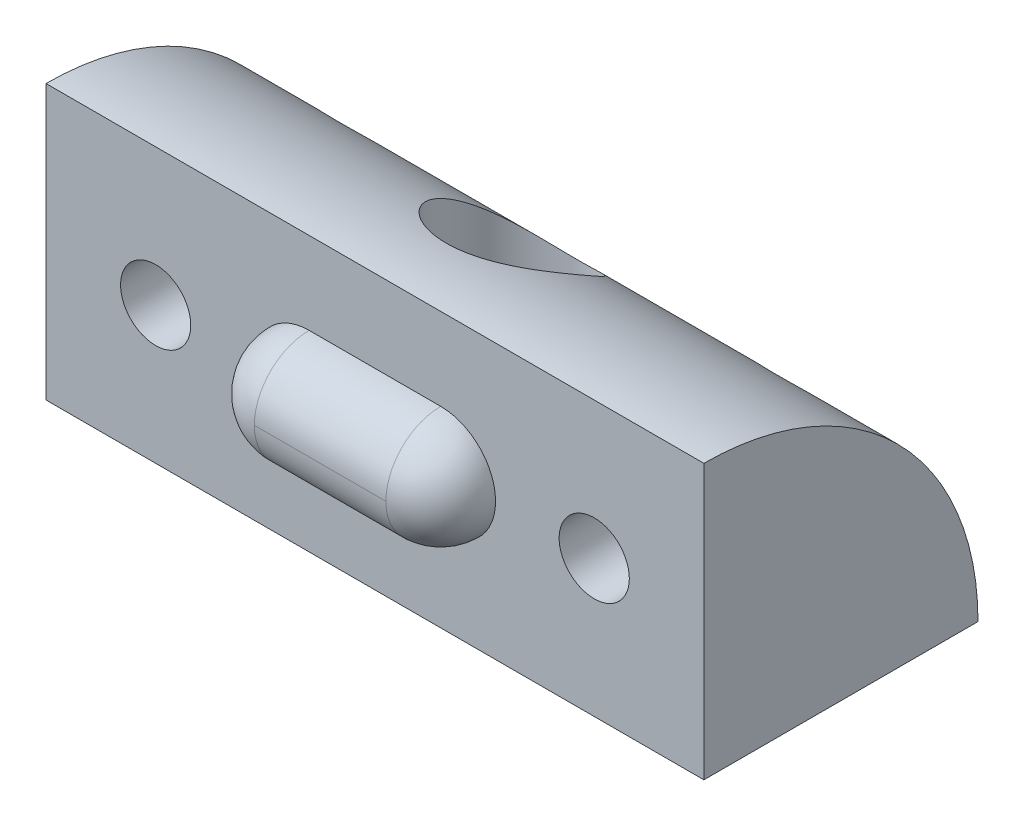
SolidWorks part; units mm, degrees
ref_plane "Alzado" through (0, 0, 0) normal (0, 0, 1) x (1, 0, 0)
ref_plane "Planta" through (0, 0, 0) normal (0, 1, 0) x (1, 0, 0)
ref_plane "Vista lateral" through (0, 0, 0) normal (1, 0, 0) x (0, 0, -1)
sketch "Croquis1" plane through (0, 0, 0) normal (1, 0, 0) x (0, 0, -1)
  line L0 (0, 0) -> (0, 12.5)
  line L1 (0, 0) -> (12.5, 0)
  arc A0 (12.5, 0) -> (0, 12.5) centre (0, 0) ccw
  dimension "D1" = 25
extrude "Saliente-Extruir1" add sketch "Croquis1" along normal blind 70
sketch "Croquis2" plane through (0, 0, 0) normal (0, 0, 1) x (1, 0, 0)
  line L0 (0, 6.25) -> (5, 6.25) construction
  line L1 (0, 12.5) -> (0, 0) construction
  circle A0 centre (5, 6.25) radius 1.6
  circle A1 centre (25, 6.25) radius 1.6
  circle A2 centre (45, 6.25) radius 1.6
  circle A3 centre (65, 6.25) radius 1.6
  dimension "D1" = 4
  dimension "D2" = 3.2
extrude "Cortar-Extruir1" cut sketch "Croquis2" against normal up to next
ref_plane "Plano1" through (0, 0, -4) normal (0, 0, 1) x (1, 0, 0)
sketch "Croquis3" plane through (0, 0, -4) normal (0, 0, 1) x (1, 0, 0)
  circle A0 centre (5, 6.25) radius 3
  circle A1 centre (25, 6.25) radius 3
  circle A2 centre (45, 6.25) radius 3
  circle A3 centre (65, 6.25) radius 3
  dimension "D1" = 4
extrude "Cortar-Extruir2" cut sketch "Croquis3" against normal up to next
sketch "Croquis4" plane through (0, 0, 0) normal (0, -1, 0) x (1, 0, 0)
  line L0 (70, -6.25) -> (55, -6.25) construction
  line L1 (70, 0) -> (70, -12.5) construction
  circle A0 centre (55, -6.25) radius 3
  circle A1 centre (35, -6.25) radius 3
  circle A2 centre (15, -6.25) radius 3
  dimension "D1" = 3
  dimension "D2" = 6
extrude "Cortar-Extruir3" cut sketch "Croquis4" against normal up to next
ref_plane "Plano2" through (0, 10, 0) normal (0, -1, 0) x (-1, 0, 0)
sketch "Croquis6" plane through (0, 0, 0) normal (-1, 0, 0) x (0, 0, 1)
  line L1 (0, 0) -> (-16.8618, 0)
  line L2 (0, 0) -> (0, 17.3809)
  line L3 (0, 17.3809) -> (-16.8618, 17.3809)
  line L4 (-16.8618, 0) -> (-16.8618, 17.3809)
extrude "Cortar-Extruir5" cut sketch "Croquis6" against normal blind 40
sketch "Croquis7" plane through (0, 0, 0) normal (0, 0, 1) x (1, 0, 0)
  line L0 (65, 6.25) -> (45, 6.25) construction
  line L1 (58, 8.75) -> (52, 8.75)
  line L2 (58, 3.75) -> (52, 3.75)
  line L3 (55, 3.75) -> (55, 8.75) construction
  line L4 (55, 12.5) -> (55, 6.25) construction
  line L5 (70, 12.5) -> (40, 12.5) construction
  arc A1 (58, 3.75) -> (58, 8.75) centre (58, 6.25) ccw
  arc A2 (52, 8.75) -> (52, 3.75) centre (52, 6.25) ccw
  point P14 (55, 6.25)
  dimension "D1" = 6
  dimension "D2" = 5
extrude "Saliente-Extruir2" add sketch "Croquis7" along normal blind 2.5
fillet "Redondeo1" radius 2.5 4 edges at (55, 3.75, 2.5) (49.5, 6.25, 2.5) (55, 8.75, 2.5) (60.5, 6.25, 2.5)
